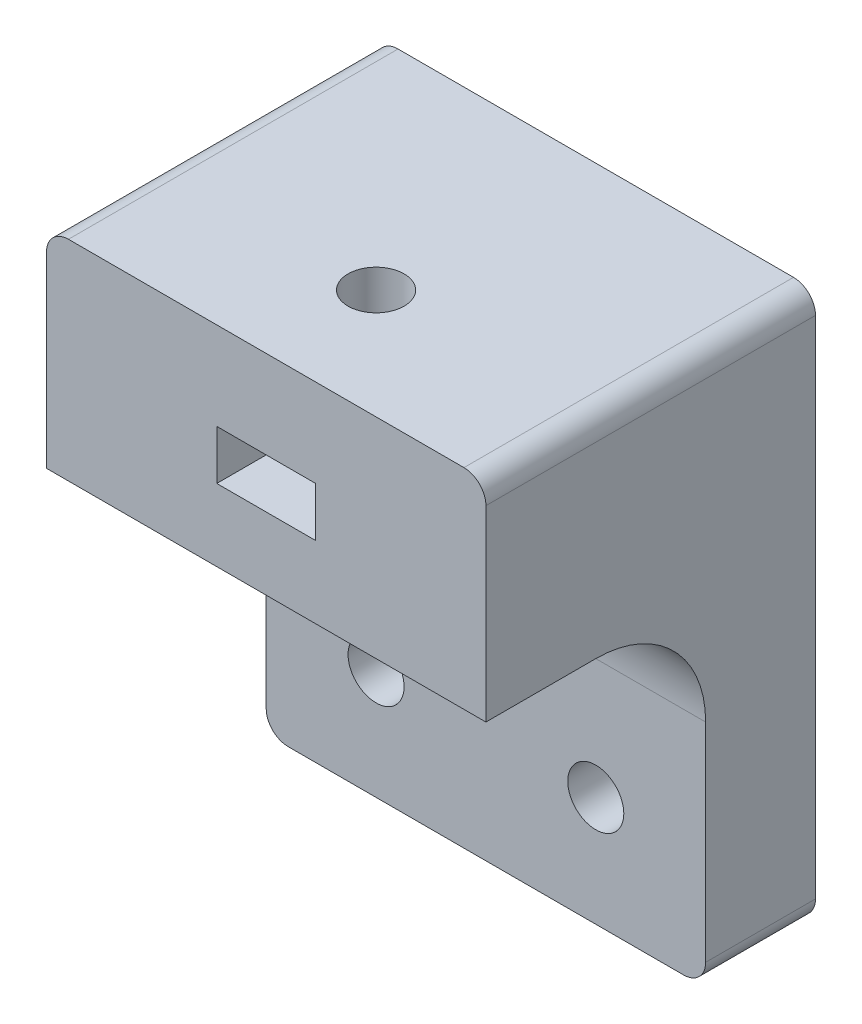
SolidWorks part; units mm, degrees
ref_plane "前视基准面" through (0, 0, 0) normal (0, 0, 1) x (1, 0, 0)
ref_plane "上视基准面" through (0, 0, 0) normal (0, 1, 0) x (1, 0, 0)
ref_plane "右视基准面" through (0, 0, 0) normal (1, 0, 0) x (0, 0, -1)
sketch "草图1" plane through (0, 0, 0) normal (0, 1, 0) x (1, 0, 0)
  line L1 (-14.8649, 16.7568) -> (25.1351, 16.7568)
  line L2 (-14.8649, 16.7568) -> (-14.8649, -13.2432)
  line L3 (-14.8649, -13.2432) -> (25.1351, -13.2432)
  line L4 (25.1351, 16.7568) -> (25.1351, -13.2432)
  dimension "D1" = 30
  dimension "D2" = 40
extrude "凸台-拉伸1" add sketch "草图1" along normal blind 50
sketch "草图2" plane through (0, 0, 13.2432) normal (0, 0, 1) x (1, 0, 0)
  line L0 (-14.8649, 50) -> (-14.8649, 0) construction
  line L1 (25.1351, 50) -> (25.1351, 0) construction
  circle A0 centre (-4.8649, 10) radius 2.55
  circle A1 centre (15.1351, 10) radius 2.55
  dimension "D1" = 5.1
  dimension "D2" = 10
  dimension "D3" = 10
extrude "切除-拉伸1" cut sketch "草图2" against normal through all
sketch "草图3" plane through (0, 0, 13.2432) normal (0, 0, 1) x (1, 0, 0)
  circle A0 centre (-4.8649, 10) radius 4.5
  circle A1 centre (15.1351, 10) radius 4.5
  dimension "D1" = 9
  dimension "D2" = 9
extrude "切除-拉伸2" cut sketch "草图3" against normal blind 20
sketch "草图4" plane through (0, 50, 0) normal (0, 1, 0) x (1, 0, 0)
  line L0 (25.1351, -13.2432) -> (25.1351, 16.7568) construction
  circle A0 centre (5.1351, -3.2432) radius 2.55
  dimension "D1" = 20
  dimension "D2" = 5.1
extrude "切除-拉伸3" cut sketch "草图4" against normal through all
sketch "草图5" plane through (0, 0, 13.2432) normal (0, 0, 1) x (1, 0, 0)
  line L0 (25.1351, 50) -> (25.1351, 0) construction
  line L1 (0.6351, 42) -> (9.6351, 42)
  line L2 (0.6351, 42) -> (0.6351, 37.5)
  line L3 (0.6351, 37.5) -> (9.6351, 37.5)
  line L4 (9.6351, 42) -> (9.6351, 37.5)
  line L5 (-14.8649, 50) -> (25.1351, 50) construction
  dimension "D1" = 9
  dimension "D2" = 4.5
  dimension "D3" = 15.5
  dimension "D4" = 8
extrude "切除-拉伸4" cut sketch "草图5" against normal blind 15
sketch "草图7" plane through (0, 0, 13.2432) normal (0, 0, 1) x (1, 0, 0)
  line L1 (-14.8649, 0) -> (25.1351, 0)
  line L2 (-14.8649, 0) -> (-14.8649, 30.9412)
  line L3 (-14.8649, 30.9412) -> (25.1351, 30.9412)
  line L4 (25.1351, 0) -> (25.1351, 30.9412)
extrude "切除-拉伸5" cut sketch "草图7" against normal blind 20
fillet "圆角1" radius 10 1 edges at (5.1351, 30.9412, -6.7568)
fillet "圆角2" radius 2 4 edges at (25.1351, 0, -11.7568) (25.1351, 50, -1.7568) (-14.8649, 50, -1.7568) (-14.8649, 0, -11.7568)
